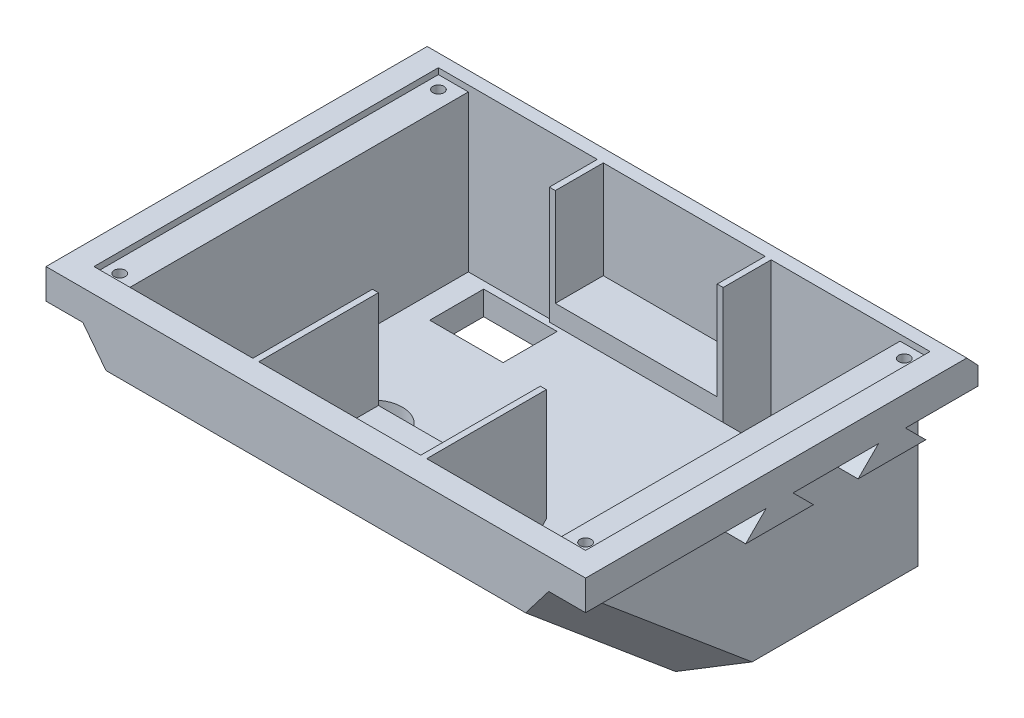
SolidWorks part; units mm, degrees
ref_plane "Front Plane" through (0, 0, 0) normal (0, 0, 1) x (1, 0, 0)
ref_plane "Top Plane" through (0, 0, 0) normal (0, 1, 0) x (1, 0, 0)
ref_plane "Right Plane" through (0, 0, 0) normal (1, 0, 0) x (0, 0, -1)
sketch "Sketch1" plane through (0, 0, 0) normal (0, 1, 0) x (1, 0, 0)
  line L5 (40, -32.725) -> (-40, -32.725)
  line L6 (40, -32.725) -> (40, 32.725)
  line L16 (40, 32.725) -> (-40, 32.725)
  line L18 (-40, -32.725) -> (-40, 32.725)
  line L19 (40, -32.725) -> (-40, 32.725) construction
  line L20 (40, 32.725) -> (-40, -32.725) construction
  point P0 (0, 0)
  dimension "D1" = 65.45
  dimension "D2" = 80
extrude "Boss-Extrude1" add sketch "Sketch1" along normal blind 31
sketch "Sketch5" plane through (-40, 0, 0) normal (-1, 0, 0) x (0, 0, 1)
  line L0 (-32.725, 31) -> (-20.625, 31)
  line L1 (-32.725, 31) -> (32.725, 31) construction
  line L2 (32.725, 31) -> (8.005, 31)
  line L3 (-20.625, 31) -> (8.005, 31)
  line L4 (-32.725, 31) -> (-32.725, 26)
  line L5 (-32.725, 31) -> (-32.725, 0) construction
  line L6 (-32.725, 26) -> (-20.625, 26)
  line L7 (32.725, 31) -> (32.725, 0) construction
  line L8 (32.725, 26) -> (32.725, 31)
  line L9 (-12.725, 22.6) -> (-16.125, 26)
  line L10 (-24.025, 22.6) -> (-12.725, 22.6)
  line L11 (-24.025, 22.6) -> (-20.625, 26)
  line L12 (-5.2797, 22.6) -> (-1.8797, 26)
  line L13 (-9.0023, 17.8446) -> (-9.0023, 22.9089) construction
  line L14 (6.0203, 22.6) -> (-5.2797, 22.6)
  line L15 (6.0203, 22.6) -> (2.6203, 26)
  line L16 (-16.125, 26) -> (-1.8797, 26)
  line L17 (2.6203, 26) -> (32.725, 26)
  dimension "D1" = 12.1
  dimension "D2" = 4.5
  dimension "24.72" = 24.72
  dimension "D3" = 45
  dimension "D4" = 45
  dimension "D5" = 11.3
  dimension "D6" = 5
  dimension "D7" = 12.1
  dimension "D8" = 3.7227
extrude "Boss-Extrude3" add sketch "Sketch5" along normal blind 5
mirror "Mirror1" about plane through (0, 0, 0) normal (1, 0, 0) of "Boss-Extrude3"
chamfer "Chamfer2" distance 25 angle 40 1 edges at (0, 0, 32.725) first distance on face at (0, 0, 0)
shell "Shell2" thickness 4 removed face at (0, 31, 0)
sketch "Sketch6" plane through (0, 4, 24.6326) normal (0, 1, 0) x (1, 0, 0)
  line L0 (0, 7.5826) -> (0, 41.6826) construction
  circle A1 centre (22, 23.4533) radius 4.8687
  circle A2 centre (-22, 23.4533) radius 4.8687
extrude "Cut-Extrude1" cut sketch "Sketch6" against normal blind 5
sketch "Sketch7" plane through (0, 0, -28.725) normal (0, 0, 1) x (1, 0, 0)
  line L0 (41, 31) -> (-41, 31) construction
  line L1 (-14.5, 13.5) -> (14.5, 13.5)
  line L2 (-14.5, 13.5) -> (-14.5, 31)
  line L4 (14.5, 13.5) -> (14.5, 31)
  line L5 (-14.5, 13.5) -> (-13.5, 14.7069) construction
  line L7 (-14.5, 31) -> (-13.5, 31)
  line L8 (-13.5, 14.7069) -> (13.5, 14.7069)
  line L9 (-13.5, 14.7069) -> (-13.5, 31)
  line L11 (13.5, 14.7069) -> (13.5, 31)
  line L14 (13.5, 31) -> (14.5, 31)
  line L15 (13.5, 14.7069) -> (14.5, 13.5) construction
  point P0 (0, 31)
  point P7 (0, 31)
  dimension "D1" = 29
  dimension "D2" = 27
  dimension "D3" = 17.5
extrude "Boss-Extrude4" add sketch "Sketch7" along normal blind 8
sketch "Sketch8" plane through (0, 0, -20.725) normal (0, 0, 1) x (1, 0, 0)
  line L0 (14.5, 13.5) -> (14.5, 31) construction
  line L1 (-13.5, 31) -> (-14.5, 31)
  line L2 (-13.5, 31) -> (-13.5, 14.7069)
  line L3 (-13.5, 13.5) -> (-14.5, 13.5)
  line L4 (-14.5, 31) -> (-14.5, 13.5)
  line L5 (-14.5, 13.5) -> (14.5, 13.5)
  line L6 (-14.5, 13.5) -> (-14.5, 14.7069)
  line L7 (-13.5, 14.7069) -> (13.5, 14.7069)
  line L8 (14.5, 13.5) -> (14.5, 14.7069)
  line L9 (13.5, 31) -> (13.5, 14.7069) construction
  line L10 (14.5, 13.5) -> (13.5, 13.5)
  line L11 (14.5, 13.5) -> (14.5, 31)
  line L12 (14.5, 31) -> (13.5, 31)
  line L13 (13.5, 14.7069) -> (13.5, 31)
  line M1 (-14.5, 31) -> (-14.5, 13.5)
  line M2 (-14.5, 13.5) -> (14.5, 13.5)
  line M3 (14.5, 13.5) -> (14.5, 31)
  line M4 (14.5, 31) -> (13.5, 31)
  line M5 (13.5, 31) -> (13.5, 14.7069)
  line M6 (13.5, 14.7069) -> (-13.5, 14.7069)
  line M7 (-13.5, 14.7069) -> (-13.5, 31)
  line M8 (-13.5, 31) -> (-14.5, 31)
extrude "Boss-Extrude5" add sketch "Sketch8" along normal up to next from offset 29.5 contours L4 L5 M8 M1 M2 M3 M4 M5 M6 M7 region at (-13.8387, 22.8534, -20.725)
sketch "Sketch10" plane through (0, 0, 0) normal (0, -1, 0) x (1, 0, 0)
  line L0 (0, -17.05) -> (0, 17.05) construction
  line L1 (-32.25, -18.525) -> (-20, -18.525)
  line L2 (-32.25, -18.525) -> (-32.25, -27.525)
  line L3 (-32.25, -27.525) -> (-20, -27.525)
  line L4 (-20, -18.525) -> (-20, -27.525)
  line L5 (20, -18.525) -> (20, -27.525)
  line L6 (32.25, -27.525) -> (20, -27.525)
  line L7 (32.25, -18.525) -> (32.25, -27.525)
  line L8 (32.25, -18.525) -> (20, -18.525)
  line L9 (40, -32.725) -> (-40, -32.725) construction
  line L10 (-36, -28.725) -> (-36, 6.2691) construction
  dimension "D1" = 5.2
  dimension "D2" = 3.75
  dimension "D3" = 9
  dimension "D4" = 16
extrude "Cut-Extrude2" cut sketch "Sketch10" against normal blind 6
chamfer "Chamfer3" distance 2 angle 43 1 edges at (0, 31, -32.725) first distance on face at (0, 20.75, -32.725)
chamfer "Chamfer4" distance 10 angle 45 1 edges at (0, 13.5, 17.5908) first distance on face at (0, 13.5, 13.1829)
chamfer "Chamfer5" distance 10 angle 45 1 edges at (0, 13.5, -28.725)
chamfer "Chamfer7" distance 5 angle 45 4 edges at (40, 10.4887, 20.225) (-40, 10.4887, 20.225) (-40, 13, -32.725) (40, 13, -32.725)
sketch "Sketch11" plane through (0, 30, 0) normal (0, 1, 0) x (1, 0, 0)
  line L0 (14.5, -28.725) -> (41, -28.725) construction
  line L1 (41, -28.725) -> (41, 28.725) construction
  line L2 (-17.05, 0) -> (17.05, 0) construction
  line L3 (0, -17.05) -> (0, 17.05) construction
  circle A0 centre (38.8496, -26.5746) radius 0.93
  circle A1 centre (38.8496, 26.5746) radius 0.93
  circle A2 centre (-38.8496, 26.5746) radius 0.93
  circle A3 centre (-38.8496, -26.5746) radius 0.93
  dimension "D1" = 1.86
  dimension "D2" = 2.1504
  dimension "D3" = 2.1504
extrude "Cut-Extrude3" cut sketch "Sketch11" against normal blind 7
